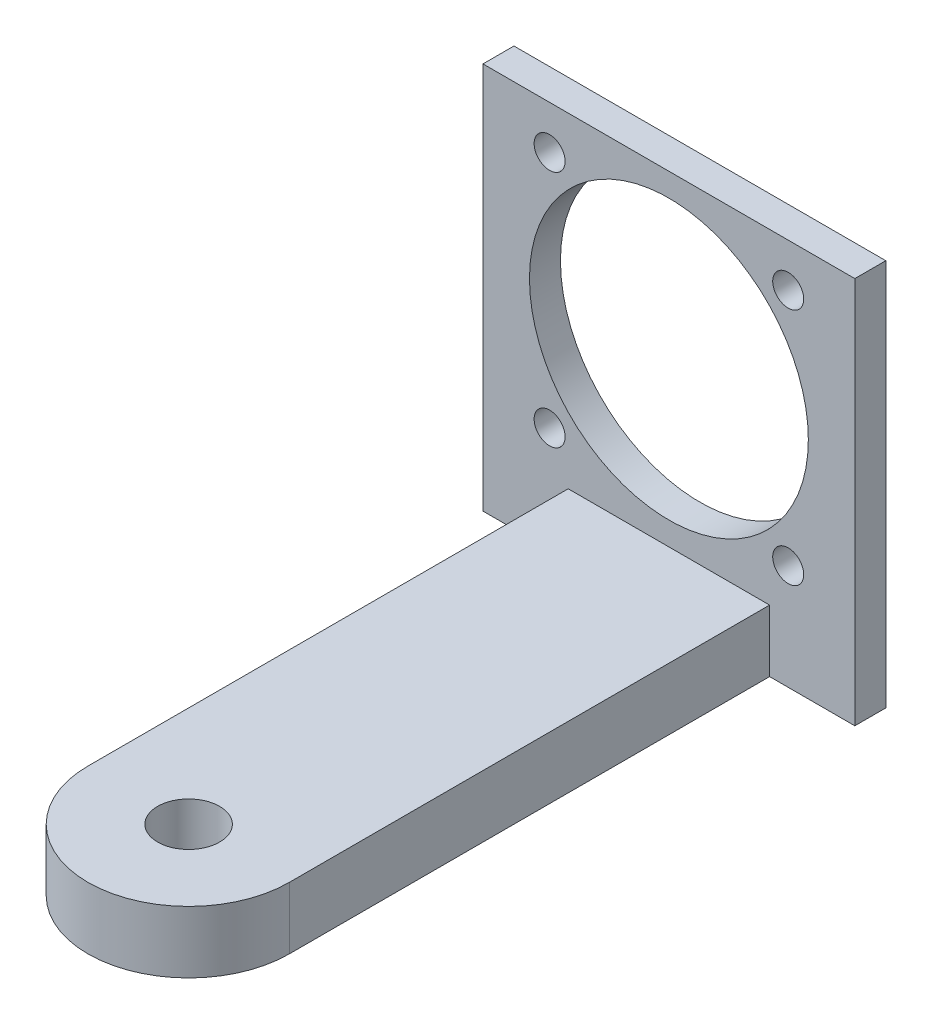
SolidWorks part; units mm, degrees
material "3.0205 (EN-AW 1200)"
ref_plane "前视基准面" through (0, 0, 0) normal (0, 0, 1) x (1, 0, 0)
ref_plane "上视基准面" through (0, 0, 0) normal (0, 1, 0) x (1, 0, 0)
ref_plane "右视基准面" through (0, 0, 0) normal (1, 0, 0) x (0, 0, -1)
sketch "草图1" plane through (0, 0, 0) normal (0, 1, 0) x (1, 0, 0)
  line L1 (5, 0) -> (2.5, 4.3301)
  line L2 (2.5, 4.3301) -> (-2.5, 4.3301)
  line L3 (-2.5, 4.3301) -> (-5, 0)
  line L4 (-5, 0) -> (-2.5, -4.3301)
  line L5 (-2.5, -4.3301) -> (2.5, -4.3301)
  line L6 (5, 0) -> (2.5, -4.3301)
sketch "草图2" plane through (0, 0, 0) normal (0, 1, 0) x (1, 0, 0)
  circle A0 centre (0, 0) radius 6.5
extrude "凸台-拉伸1" add sketch "草图2" along normal blind 4
sketch "草图3" plane through (0, 4, 0) normal (0, 1, 0) x (1, 0, 0)
  circle A0 centre (0, 0) radius 2
extrude "切除-拉伸2" cut sketch "草图3" against normal through all
sketch "草图4" plane through (0, 4, 0) normal (0, 1, 0) x (1, 0, 0)
  line L1 (6.5, 31) -> (3.8991, 31)
  line L3 (-6.5, 0) -> (-6.5, 31)
  line L4 (-6.5, 31) -> (-4.1009, 31)
  line L7 (-6.5, 0) -> (6.5, 0)
  line L8 (6.5, 0) -> (6.5, 31)
  line L11 (-4.1009, 31) -> (3.8991, 31)
  circle A0 centre (0, 0) radius 6.5 construction
  circle A1 centre (0, 0) radius 6.5
  circle M6 centre (0, 0) radius 6.5
extrude "凸台-拉伸2" add sketch "草图4" against normal blind 4 contours L4 L3 M6 | L8 L1 M6 region at (0, 4, -18.0119)
sketch "草图6" plane through (0, 0, -31) normal (0, 0, -1) x (-1, 0, 0)
  line L5 (-15.5564, 5.1908) -> (-3.328, -1.1893)
sketch "草图18" plane through (0, 0, 0) normal (0, -1, 0) x (1, 0, 0)
  circle A0 centre (0, 0) radius 2.5328
sketch "草图20" plane through (0, 0, 0) normal (1, 0, 0) x (0, 0, -1)
  line L0 (0, 4) -> (0, 3)
  circle A0 centre (0, 3) radius 1.5
sketch "草图21" plane through (0, 0, -31) normal (0, 0, -1) x (-1, 0, 0)
  line L0 (0, 0) -> (12, 0)
  line L1 (12, 0) -> (12, 25)
  line L2 (12, 25) -> (-12, 25)
  line L3 (-12, 25) -> (-12, 0)
  line L4 (-12, 0) -> (0, 0)
extrude "凸台-拉伸3" add sketch "草图21" along normal blind 2
sketch "草图22" plane through (0, 0, -31) normal (0, 0, 1) x (1, 0, 0)
  line L0 (-6.5, 4) -> (-12, 4)
  line L1 (-12, 0) -> (-12, 25) construction
  line L2 (0, 4) -> (0, 25)
  line L3 (-6.5, 4) -> (6.5, 4) construction
  line L4 (-12, 25) -> (12, 25) construction
  line L5 (0, 14.5) -> (7.7, 14.5)
  line L6 (7.7, 14.5) -> (7.7, 22.2)
  line L7 (7.7, 22.2) -> (-7.7, 22.2)
  line L8 (-7.7, 22.2) -> (-7.7, 6.8)
  line L9 (-7.7, 6.8) -> (7.7, 6.8)
  circle A0 centre (0, 14.5) radius 9
  circle A1 centre (7.7, 22.2) radius 1
  circle A2 centre (-7.7, 22.2) radius 1
  circle A3 centre (-7.7, 6.8) radius 1
  circle A4 centre (7.7, 6.8) radius 1
extrude "切除-拉伸4" cut sketch "草图22" against normal blind 2 contours A0 | A3 | A4 | A1 | A2
